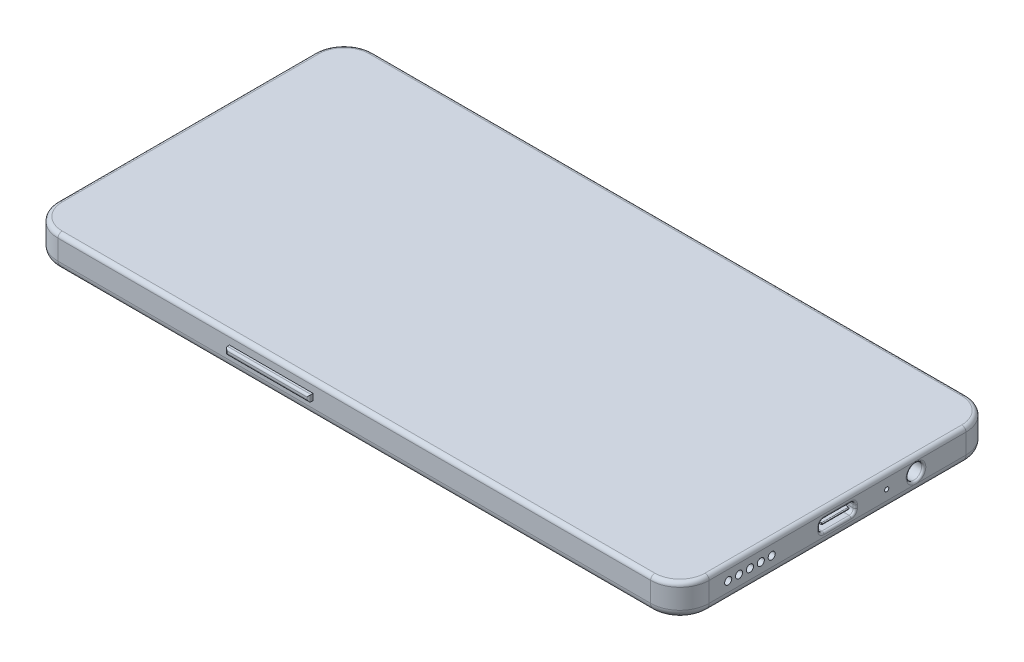
SolidWorks part; units mm, degrees
ref_plane "Front Plane" through (0, 0, 0) normal (0, 0, 1) x (1, 0, 0)
ref_plane "Top Plane" through (0, 0, 0) normal (0, 1, 0) x (1, 0, 0)
ref_plane "Right Plane" through (0, 0, 0) normal (1, 0, 0) x (0, 0, -1)
sketch "Sketch1" plane through (0, 0, 0) normal (0, 1, 0) x (1, 0, 0)
  line L1 (-77.85, -37.7) -> (77.85, -37.7)
  line L2 (-77.85, -37.7) -> (-77.85, 37.7)
  line L3 (-77.85, 37.7) -> (77.85, 37.7)
  line L4 (77.85, -37.7) -> (77.85, 37.7)
  line L5 (0, 37.7) -> (0, -37.7) construction
  line L6 (-77.85, 0) -> (77.85, 0) construction
  point P0 (0, 0)
  dimension "D1" = 155.7
  dimension "D2" = 75.4
extrude "Boss-Extrude1" add sketch "Sketch1" along normal blind 7.75
fillet "Fillet1" radius 7 4 edges at (-77.85, 3.875, -37.7) (77.85, 3.875, -37.7) (77.85, 3.875, 37.7) (-77.85, 3.875, 37.7)
fillet "Fillet2" radius 1 8 edges at (-75.7997, 7.75, 35.6497) (-77.85, 7.75, 0) (-75.7997, 7.75, -35.6497) (0, 7.75, -37.7) (75.7997, 7.75, -35.6497) (77.85, 7.75, 0) (75.7997, 7.75, 35.6497) (0, 7.75, 37.7)
fillet "Fillet3" radius 2 8 edges at (-75.7997, 0, 35.6497) (-77.85, 0, 0) (-75.7997, 0, -35.6497) (0, 0, -37.7) (75.7997, 0, -35.6497) (77.85, 0, 0) (75.7997, 0, 35.6497) (0, 0, 37.7)
sketch "Sketch2" plane through (0, 0, 0) normal (0, -1, 0) x (1, 0, 0)
  line L0 (-49.85, 0) -> (-59.85, 0) construction
  line L1 (-49.85, -5.575) -> (-59.85, -5.575)
  line L2 (-49.85, 5.575) -> (-59.85, 5.575)
  line L3 (-77.85, -30.7) -> (-77.85, 30.7) construction
  arc A0 (-49.85, -5.575) -> (-49.85, 5.575) centre (-49.85, 0) ccw
  arc A1 (-59.85, 5.575) -> (-59.85, -5.575) centre (-59.85, 0) ccw
  point P3 (-54.85, 0)
  point P8 (0, 0)
  point P9 (-48.962, 0)
  dimension "D1" = 10
  dimension "D3" = 18
  dimension "D2" = 11.15
extrude "Boss-Extrude2" add sketch "Sketch2" along normal blind 0.6
sketch "Sketch3" plane through (0, -0.6, 0) normal (0, -1, 0) x (1, 0, 0)
  line L0 (-49.85, 5.575) -> (-59.85, 5.575) construction
  line L3 (-59.85, -5.575) -> (-49.85, -5.575) construction
  circle A0 centre (-49.8619, 0.0106) radius 4
  circle A1 centre (-59.8619, 0) radius 4
  arc A4 (-59.85, 5.575) -> (-59.85, -5.575) centre (-59.85, 0) ccw construction
  arc A5 (-49.85, -5.575) -> (-49.85, 5.575) centre (-49.85, 0) ccw construction
  point P9 (-55.2799, 0)
  point P10 (-59.8672, 0)
  dimension "D1" = 8
  dimension "D2" = 8
  dimension "D3" = 10
  dimension "D4" = 5.575
  dimension "D5" = 5.575
  dimension "D6" = 0.0119
  dimension "D7" = 0.0159
extrude "Cut-Extrude1" cut sketch "Sketch3" against normal blind 0.1
sketch "Sketch4" plane through (0, -0.5, 0) normal (0, -1, 0) x (1, 0, 0)
  circle A0 centre (-49.8619, 0.0106) radius 2
  circle A1 centre (-59.8619, 0) radius 2
  dimension "D1" = 4
  dimension "D2" = 4
extrude "Cut-Extrude2" cut sketch "Sketch4" against normal blind 0.1
sketch "Sketch5" plane through (0, 0, 0) normal (0, -1, 0) x (1, 0, 0)
  line L0 (-39.8619, -2.6476) -> (-39.8619, 2.6476) construction
  line L1 (-41.1119, -2.6476) -> (-41.1119, 2.6476)
  line L2 (-38.6119, -2.6476) -> (-38.6119, 2.6476)
  line L3 (-75.85, 30.7) -> (-75.85, -30.7) construction
  line L4 (70.85, 35.7) -> (-70.85, 35.7) construction
  line L5 (-70.85, -35.7) -> (70.85, -35.7) construction
  arc A0 (-41.1119, -2.6476) -> (-38.6119, -2.6476) centre (-39.8619, -2.6476) ccw
  arc A1 (-38.6119, 2.6476) -> (-41.1119, 2.6476) centre (-39.8619, 2.6476) ccw
  circle A2 centre (-49.8619, 0.0106) radius 2 construction
  point P2 (-39.8619, 0)
  point P7 (0, 0)
  point P8 (0, 0)
  point P14 (-36.4988, -0.6391)
  point P15 (-36.4988, -0.5022)
  dimension "D1" = 5.2952
  dimension "D3" = 35.7
  dimension "D2" = 2.5
  dimension "D4" = 35.7
  dimension "D5" = 10
extrude "Cut-Extrude3" cut sketch "Sketch5" against normal blind 0.1
sketch "Sketch6" plane through (0, 0, 0) normal (0, -1, 0) x (1, 0, 0)
  line L0 (-38.6119, -2.6476) -> (-38.6119, 2.6476) construction
  line L1 (-29.2716, -6.25) -> (-36.1119, -6.25)
  line L2 (-29.2716, -6.25) -> (-29.2716, 6.25)
  line L3 (-29.2716, 6.25) -> (-36.1119, 6.25)
  line L4 (-36.1119, -6.25) -> (-36.1119, 6.25)
  line L5 (-32.6917, 6.25) -> (-32.6917, -6.25) construction
  line L6 (-29.2716, 0) -> (-36.1119, 0) construction
  line L7 (70.85, 35.7) -> (-70.85, 35.7) construction
  line L8 (-70.85, -35.7) -> (70.85, -35.7) construction
  point P0 (-32.6917, 0)
  dimension "D1" = 12.5
  dimension "D2" = 6.8403
  dimension "D3" = 2.5
  dimension "D4" = 29.45
  dimension "D5" = 29.45
extrude "Cut-Extrude4" cut sketch "Sketch6" against normal blind 0.1
fillet "Fillet4" radius 2 4 edges at (-29.2716, 0.05, 6.25) (-29.2716, 0.05, -6.25) (-36.1119, 0.05, 6.25) (-36.1119, 0.05, -6.25)
fillet "Fillet5" radius 0.5 8 edges at (-35.5261, 0.1, 5.6642) (-32.6917, 0.1, 6.25) (-29.8574, 0.1, 5.6642) (-29.2716, 0.1, 0) (-29.8574, 0.1, -5.6642) (-32.6917, 0.1, -6.25) (-35.5261, 0.1, -5.6642) (-36.1119, 0.1, 0)
sketch "Sketch7" plane through (0, 0, -37.7) normal (0, 0, 1) x (1, 0, 0)
  line L0 (-77.85, 2) -> (-77.85, 6.75) construction
  line L1 (-17.85, 3.375) -> (-29.85, 3.375)
  line L2 (-17.85, 3.375) -> (-17.85, 5.375)
  line L3 (-17.85, 5.375) -> (-29.85, 5.375)
  line L4 (-29.85, 3.375) -> (-29.85, 5.375)
  line L5 (-23.85, 5.375) -> (-23.85, 3.375) construction
  line L6 (-17.85, 4.375) -> (-29.85, 4.375) construction
  line L9 (-70.85, 2) -> (70.85, 2) construction
  line L10 (70.85, 6.75) -> (-70.85, 6.75) construction
  point P0 (-23.85, 4.375)
  point P6 (-77.85, 4.375)
  dimension "D1" = 60
  dimension "D2" = 2
  dimension "D3" = 1.375
  dimension "D4" = 1.375
  dimension "D5" = 12
extrude "Boss-Extrude3" add sketch "Sketch7" along normal blind 0.2 and the other way blind 0.2
fillet "Fillet6" radius 1 4 edges at (-17.85, 3.375, -37.8) (-17.85, 5.375, -37.8) (-29.85, 3.375, -37.8) (-29.85, 5.375, -37.8)
sketch "Sketch8" plane through (0, 0, -37.7) normal (0, 0, -1) x (-1, 0, 0)
  line L0 (48.115, 4.375) -> (39.115, 4.375) construction
  line L1 (48.115, 3.475) -> (39.115, 3.475)
  line L2 (48.115, 5.275) -> (39.115, 5.275)
  line L3 (-70.85, 2) -> (70.85, 2) construction
  line L5 (70.85, 6.75) -> (-70.85, 6.75) construction
  arc A0 (48.115, 3.475) -> (48.115, 5.275) centre (48.115, 4.375) ccw
  arc A1 (39.115, 5.275) -> (39.115, 3.475) centre (39.115, 4.375) ccw
  point P2 (43.615, 4.375)
  dimension "D1" = 9
  dimension "D2" = 2.375
  dimension "D3" = 2.375
extrude "Cut-Extrude5" cut sketch "Sketch8" against normal blind 0.5
sketch "Sketch9" plane through (0, 0, -37.2) normal (0, 0, -1) x (-1, 0, 0)
  line L0 (47.9183, 4.375) -> (39.5183, 4.375) construction
  line L1 (47.9183, 3.475) -> (39.5183, 3.475)
  line L2 (47.9183, 5.275) -> (39.5183, 5.275)
  line L3 (39.115, 3.475) -> (48.115, 3.475) construction
  line L4 (48.115, 5.275) -> (39.115, 5.275) construction
  arc A0 (47.9183, 3.475) -> (47.9183, 5.275) centre (47.9183, 4.375) ccw
  arc A1 (39.5183, 5.275) -> (39.5183, 3.475) centre (39.5183, 4.375) ccw
  point P4 (43.7183, 4.375)
  point P9 (44.0884, 4.3914)
  point P12 (43.7183, 4.1416)
  dimension "D1" = 8.4
extrude "Boss-Extrude4" add sketch "Sketch9" along normal blind 0.6
fillet "Fillet7" radius 0.1 4 edges at (-43.7183, 3.475, -37.8) (-38.6183, 4.375, -37.8) (-43.7183, 5.275, -37.8) (-48.8183, 4.375, -37.8)
sketch "Sketch11" plane through (77.85, 0, 0) normal (1, 0, 0) x (0, 0, -1)
  line L0 (30.7, 6.75) -> (-30.7, 6.75) construction
  line L1 (4.25, 5.75) -> (-4.25, 5.75)
  line L2 (4.25, 5.75) -> (4.25, 3)
  line L3 (4.25, 3) -> (-4.25, 3)
  line L4 (-4.25, 5.75) -> (-4.25, 3)
  line L5 (0, 3) -> (0, 5.75) construction
  line L6 (4.25, 4.375) -> (-4.25, 4.375) construction
  line L7 (-30.7, 2) -> (30.7, 2) construction
  line L8 (30.7, 2) -> (30.7, 6.75) construction
  line L9 (-30.7, 6.75) -> (-30.7, 2) construction
  point P0 (0, 4.375)
  dimension "D1" = 8.5
  dimension "D2" = 2.75
  dimension "D3" = 1
  dimension "D4" = 1
  dimension "D5" = 26.45
  dimension "D6" = 26.45
extrude "Cut-Extrude6" cut sketch "Sketch11" against normal blind 6.5
fillet "Fillet8" radius 1 4 edges at (74.6, 5.75, 4.25) (74.6, 5.75, -4.25) (74.6, 3, 4.25) (74.6, 3, -4.25)
sketch "Sketch12" plane through (71.35, 0, 0) normal (1, 0, 0) x (0, 0, -1)
  line L0 (-3.25, 3) -> (3.25, 3) construction
  line L1 (3.3225, 4.575) -> (-3.1775, 4.575)
  line L2 (3.3225, 4.575) -> (3.3225, 4.175)
  line L3 (3.3225, 4.175) -> (-3.1775, 4.175)
  line L4 (-3.1775, 4.575) -> (-3.1775, 4.175)
  line L5 (0.0725, 4.175) -> (0.0725, 4.575) construction
  line L6 (3.3225, 4.375) -> (-3.1775, 4.375) construction
  line L7 (3.25, 5.75) -> (-3.25, 5.75) construction
  point P0 (0.0725, 4.375)
  point P6 (0.0725, 4.5809)
  dimension "D1" = 0.4
  dimension "D2" = 1.175
  dimension "D3" = 1.175
extrude "Boss-Extrude5" add sketch "Sketch12" along normal blind 6
fillet "Fillet9" radius 0.5 8 edges at (77.85, 4.375, -4.25) (77.85, 5.4571, -3.9571) (77.85, 5.75, 0) (77.85, 5.4571, 3.9571) (77.85, 4.375, 4.25) (77.85, 3.2929, 3.9571) (77.85, 3, 0) (77.85, 3.2929, -3.9571)
sketch "Sketch13" plane through (77.85, 0, 0) normal (1, 0, 0) x (0, 0, -1)
  line L0 (-4.75, 4) -> (-4.75, 4.75) construction
  line L1 (-30.7, 2) -> (30.7, 2) construction
  line L2 (30.7, 6.75) -> (-30.7, 6.75) construction
  circle A0 centre (-15.75, 4.375) radius 0.85
  circle A1 centre (-18.35, 4.375) radius 0.85
  circle A2 centre (-20.95, 4.375) radius 0.85
  circle A3 centre (-23.55, 4.375) radius 0.85
  circle A4 centre (-26.15, 4.375) radius 0.85
  point P16 (23.5492, 4.5716)
  point P17 (18.2921, 4.5664)
  point P18 (15.75, 4.5664)
  point P19 (18.3209, 4.9546)
  point P20 (18.3209, 4.9546)
  point P21 (26.0871, 4.4175)
  point P22 (20.8917, 4.5664)
  point P23 (0, 0)
  point P24 (18.3209, 4.9546)
  dimension "D1" = 1.7
  dimension "D2" = 1.7
  dimension "D3" = 1.7
  dimension "D4" = 1.7
  dimension "D5" = 1.7
  dimension "D6" = 2.6
  dimension "D7" = 2.6
  dimension "D8" = 2.6
  dimension "D9" = 2.6
  dimension "D10" = 11
  dimension "D11" = 2.375
  dimension "D12" = 2.375
  dimension "D13" = 2.375
  dimension "D14" = 2.375
  dimension "D15" = 2.375
  dimension "D16" = 2.375
extrude "Cut-Extrude7" cut sketch "Sketch13" against normal blind 6
sketch "Sketch14" plane through (77.85, 0, 0) normal (1, 0, 0) x (0, 0, -1)
  line L0 (-30.7, 2) -> (30.7, 2) construction
  line L1 (30.7, 6.75) -> (-30.7, 6.75) construction
  line L3 (4.75, 4.75) -> (4.75, 4) construction
  circle A0 centre (18.75, 4.375) radius 1.85
  point P2 (-21.9922, 4.511)
  dimension "D1" = 3.7
  dimension "D2" = 2.375
  dimension "D3" = 2.375
  dimension "D4" = 14
extrude "Cut-Extrude8" cut sketch "Sketch14" against normal blind 14
fillet "Fillet10" radius 0.5 1 edges at (77.85, 4.375, -20.6)
fillet "Fillet12" radius 0.2 4 edges at (77.35, 4.575, -0.0725) (77.35, 4.375, -3.3225) (77.35, 4.175, -0.0725) (77.35, 4.375, 3.1775)
sketch "Sketch15" plane through (77.85, 0, 0) normal (1, 0, 0) x (0, 0, -1)
  line L0 (30.7, 6.75) -> (-30.7, 6.75) construction
  line L1 (4.75, 4.75) -> (4.75, 4) construction
  circle A0 centre (11.75, 4.375) radius 0.5
  circle A1 centre (18.75, 4.375) radius 2.35 construction
  dimension "D1" = 2.375
  dimension "D2" = 7
  dimension "D3" = 7
  dimension "D4" = 1
extrude "Cut-Extrude9" cut sketch "Sketch15" against normal blind 6
sketch "Sketch16" plane through (-77.85, 0, 0) normal (-1, 0, 0) x (0, 0, 1)
  line L0 (30.7, 6.75) -> (-30.7, 6.75) construction
  line L1 (-37.7, 2) -> (-37.7, 6.75) construction
  circle A0 centre (-16.7, 4.375) radius 0.5
  dimension "D1" = 1
  dimension "D2" = 2.375
  dimension "D3" = 21
extrude "Cut-Extrude10" cut sketch "Sketch16" against normal blind 6
sketch "Sketch18" plane through (0, 0, 37.7) normal (0, 0, 1) x (1, 0, 0)
  line L0 (-70.85, 2) -> (70.85, 2) construction
  line L1 (-29.85, 5.125) -> (-9.85, 5.125)
  line L2 (-29.85, 5.125) -> (-29.85, 3.625)
  line L3 (-29.85, 3.625) -> (-9.85, 3.625)
  line L4 (-9.85, 5.125) -> (-9.85, 3.625)
  line L5 (-19.85, 3.625) -> (-19.85, 5.125) construction
  line L6 (-29.85, 4.375) -> (-9.85, 4.375) construction
  line L7 (70.85, 6.75) -> (-70.85, 6.75) construction
  line L9 (-77.85, 2) -> (-77.85, 6.75) construction
  point P0 (-19.85, 4.375)
  point P4 (-42.0759, 4.1974)
  dimension "D1" = 1.5
  dimension "D2" = 48
  dimension "D3" = 20
  dimension "D4" = 1.625
  dimension "D5" = 1.625
extrude "Boss-Extrude6" add sketch "Sketch18" along normal blind 1
fillet "Fillet13" radius 0.5 4 edges at (-19.85, 3.625, 38.7) (-29.85, 4.375, 38.7) (-19.85, 5.125, 38.7) (-9.85, 4.375, 38.7)
